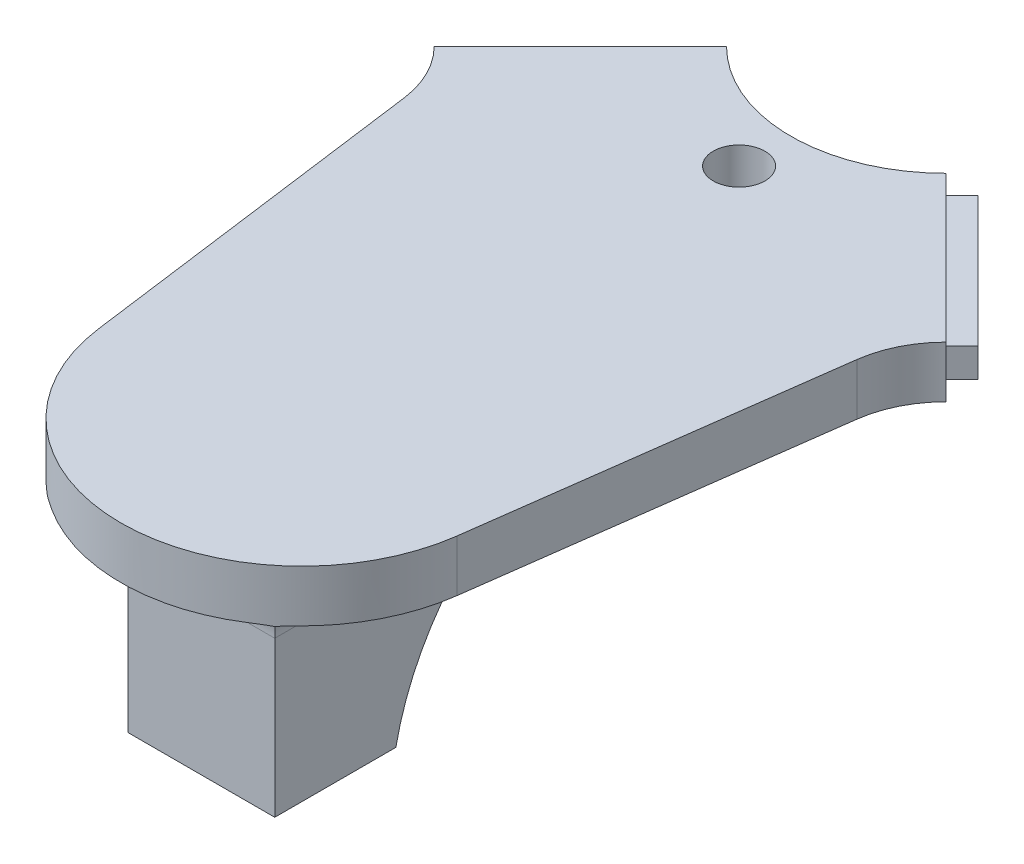
SolidWorks part; units mm, degrees
ref_plane "Front Plane" through (0, 0, 0) normal (0, 0, 1) x (1, 0, 0)
ref_plane "Top Plane" through (0, 0, 0) normal (0, 1, 0) x (1, 0, 0)
ref_plane "Right Plane" through (0, 0, 0) normal (1, 0, 0) x (0, 0, -1)
sketch "Sketch2" plane through (0, 0, 0) normal (0, 1, 0) x (1, 0, 0)
  line L0 (0, 0) -> (0, -177.8) construction
  line L1 (0, 0) -> (143.6841, -143.6841) construction
  line L2 (0, 0) -> (-143.6841, -143.6841) construction
  line L3 (0, 0) -> (0, -158.75) construction
  line L4 (-12.954, -158.242) -> (12.954, -158.242)
  line L5 (12.954, -158.242) -> (12.954, -177.8368)
  line L6 (-12.954, -158.242) -> (-12.954, -177.8368)
  line L7 (55.6463, -77.4563) -> (44.058, -164.1324)
  line L8 (-55.6463, -77.4563) -> (-44.058, -164.1324)
  line L9 (-62.8618, -62.8618) -> (-26.9408, -26.9408)
  line L10 (62.8618, -62.8618) -> (26.9408, -26.9408)
  arc A0 (-26.9408, -26.9408) -> (26.9408, -26.9408) centre (0, 0) ccw
  arc A1 (-12.954, -177.8368) -> (12.954, -177.8368) centre (0, 0) ccw
  circle A2 centre (0, 0) radius 88.9 construction
  arc A3 (62.8618, -62.8618) -> (55.6463, -77.4563) centre (80.8223, -80.8223) ccw
  arc A4 (-62.8618, -62.8618) -> (-55.6463, -77.4563) centre (-80.8223, -80.8223) cw
  arc A6 (-44.058, -164.1324) -> (44.058, -164.1324) centre (0, -158.242) ccw
  point P12 (0, -178.308)
  point P24 (0, -158.242)
  dimension "D1" = 76.2
  dimension "D11" = 177.8
  dimension "D12" = 44.45
  dimension "D13" = 25.4
  dimension "D2" = 45
  dimension "D3" = 177.8
  dimension "D4" = 158.75
  dimension "D5" = 12.954
  dimension "D6" = 12.954
  dimension "D7" = 0.508
  dimension "D8" = 203.2
  dimension "D9" = 203.2
  dimension "D10" = 20.066
extrude "Boss-Extrude1" add sketch "Sketch2" along normal blind 12.7 contours L8 A6 L7 A3 L10 A0 L9 A4 A1 L6 L4 L5 region at (0, 0, 109.5124)
sketch "Sketch3" plane through (0, 0, 0) normal (-0.7071, 0, -0.7071) x (-0.7071, 0, 0.7071)
  line L0 (88.9, 12.7) -> (38.1, 12.7) construction
  line L1 (40.64, 10.16) -> (86.36, 10.16)
  line L2 (40.64, 10.16) -> (40.64, 2.54)
  line L3 (40.64, 2.54) -> (86.36, 2.54)
  line L4 (86.36, 10.16) -> (86.36, 2.54)
  line L5 (88.9, 0) -> (38.1, 0) construction
  line L6 (38.1, 12.7) -> (38.1, 0) construction
  line L7 (88.9, 12.7) -> (88.9, 0) construction
  dimension "D1" = 2.54
  dimension "D2" = 2.54
  dimension "D3" = 2.54
  dimension "D4" = 2.54
extrude "Cut-Extrude1" cut sketch "Sketch3" against normal blind 6.35
sketch "Sketch4" plane through (0, 0, 0) normal (0.7071, 0, -0.7071) x (-0.7071, 0, -0.7071)
  line L0 (-88.9, 12.7) -> (-88.9, 0) construction
  line L1 (-86.106, 9.906) -> (-40.894, 9.906)
  line L2 (-86.106, 9.906) -> (-86.106, 2.794)
  line L3 (-86.106, 2.794) -> (-40.894, 2.794)
  line L4 (-40.894, 9.906) -> (-40.894, 2.794)
  line L5 (-38.1, 12.7) -> (-38.1, 0) construction
  line L6 (-88.9, 0) -> (-38.1, 0) construction
  line L7 (-88.9, 12.7) -> (-38.1, 12.7) construction
  dimension "D1" = 2.794
  dimension "D2" = 2.794
  dimension "D3" = 2.794
  dimension "D4" = 2.794
extrude "Boss-Extrude2" add sketch "Sketch4" along normal blind 5.588
sketch "Sketch5" plane through (0, 12.7, 0) normal (0, 1, 0) x (1, 0, 0)
  circle A0 centre (0, -158.242) radius 44.45
  arc A1 (-44.058, -164.1324) -> (44.058, -164.1324) centre (0, -158.242) ccw construction
extrude "Boss-Extrude3" add sketch "Sketch5" against normal blind 3.81
sketch "Sketch6" plane through (0, 12.7, 0) normal (0, 1, 0) x (1, 0, 0)
  circle A0 centre (0, -50.8) radius 6.35
  arc A1 (-26.9408, -26.9408) -> (26.9408, -26.9408) centre (0, 0) ccw construction
  point P5 (0, 0)
  dimension "D1" = 12.7
  dimension "D2" = 50.8
extrude "Cut-Extrude2" cut sketch "Sketch6" against normal through all contours A0
sketch "Sketch9" plane through (0, 0, 0) normal (0, -1, 0) x (1, 0, 0)
  line L0 (-12.954, 158.242) -> (12.954, 158.242) construction
  line L1 (-18.034, 182.9168) -> (18.034, 182.9168)
  line L2 (-18.034, 182.9168) -> (-18.034, 153.162)
  line L3 (-18.034, 153.162) -> (18.034, 153.162)
  line L4 (18.034, 182.9168) -> (18.034, 153.162)
  line L5 (12.954, 158.242) -> (12.954, 177.8368) construction
  line L6 (-12.954, 158.242) -> (-12.954, 177.8368) construction
  line L7 (-12.954, 158.242) -> (12.954, 158.242)
  line L8 (12.954, 158.242) -> (12.954, 177.8368)
  line L9 (-12.954, 158.242) -> (-12.954, 177.8368)
  arc A0 (12.954, 177.8368) -> (-12.954, 177.8368) centre (0, 0) ccw construction
  arc A1 (12.954, 177.8368) -> (-12.954, 177.8368) centre (0, 0) ccw
  point P6 (-18.034, 153.162)
  dimension "D1" = 5.08
  dimension "D2" = 5.08
  dimension "D3" = 5.08
  dimension "D4" = 5.08
extrude "Boss-Extrude5" add sketch "Sketch9" along normal blind 50.8
fillet "Fillet3" radius 63.5 1 edges at (0, 0, 153.162)
fillet "Fillet4" radius 12.7 2 edges at (18.034, 0, 136.9309) (-18.034, 0, 136.9309)
fillet "Fillet5" radius 12.7 1 edges at (0, 0, 182.9168)
